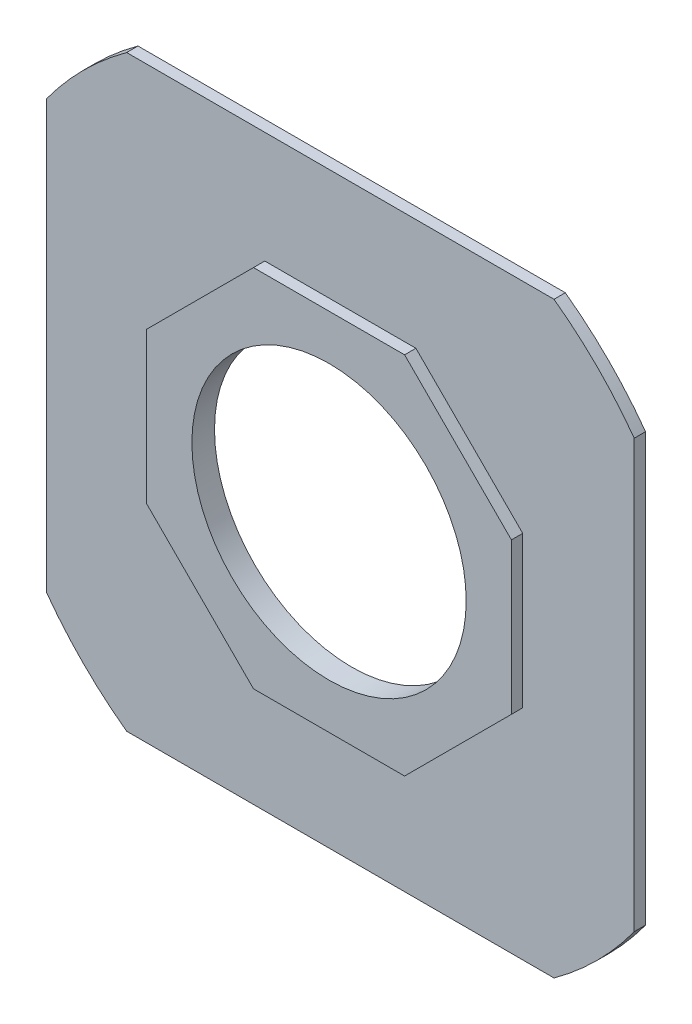
SolidWorks part; units mm, degrees
ref_plane "Front Plane" through (0, 0, 0) normal (0, 0, 1) x (1, 0, 0)
ref_plane "Top Plane" through (0, 0, 0) normal (0, 1, 0) x (1, 0, 0)
ref_plane "Right Plane" through (0, 0, 0) normal (1, 0, 0) x (0, 0, -1)
sketch "Sketch1" plane through (0, 0, 0) normal (0, 0, 1) x (1, 0, 0)
  line L1 (21.2077, 51.2) -> (-21.2077, 51.2)
  line L2 (-21.2077, 51.2) -> (-51.2, 21.2077)
  line L3 (-51.2, 21.2077) -> (-51.2, -21.2077)
  line L4 (-51.2, -21.2077) -> (-21.2077, -51.2)
  line L5 (-21.2077, -51.2) -> (21.2077, -51.2)
  line L6 (21.2077, -51.2) -> (51.2, -21.2077)
  line L7 (51.2, -21.2077) -> (51.2, 21.2077)
  line L8 (51.2, 21.2077) -> (21.2077, 51.2)
  line L9 (101.9739, -101.9739) -> (-101.9739, -101.9739)
  line L10 (101.9739, -101.9739) -> (101.9739, 101.9739)
  line L11 (101.9739, 101.9739) -> (-101.9739, 101.9739)
  line L12 (-101.9739, -101.9739) -> (-101.9739, 101.9739)
  line L13 (101.9739, -101.9739) -> (-101.9739, 101.9739) construction
  line L14 (101.9739, 101.9739) -> (-101.9739, -101.9739) construction
  circle A0 centre (0, 0) radius 38.5
  circle A1 centre (0, 0) radius 51.2 construction
  dimension "D1" = 77
  dimension "D2" = 12.7
extrude "Boss-Extrude1" add sketch "Sketch1" along normal blind 3.175 contours L7 L8 L1 L2 L3 L4 L5 L6 A0 | L12 L9 L10 L11 L8 L7 L6 L5 L4 L3 L2 L1 region at (35.1799, 35.1799, 0) region at (0, -99.0896, 0)
extrude "Boss-Extrude2" add sketch "Sketch1<3>" along normal blind 6.35 contours L7 L8 L1 L2 L3 L4 L5 L6 A0 region at (35.1799, 35.1799, 0)
sketch "Sketch1<3>" plane through (0, 0, 0) normal (0, 0, 1) x (1, 0, 0) same geometry as "Sketch1"
sketch "Sketch6" plane through (0, 0, 0) normal (0, 0, -1) x (-1, 0, 0)
  line L0 (-81, 59.4916) -> (-81, -59.4916) construction
  line L1 (-59.4916, 81) -> (59.4916, 81) construction
  line L2 (81, 59.4916) -> (81, -59.4916) construction
  line L3 (-59.4916, -81) -> (59.4916, -81) construction
  line L4 (-82.5, 59.9812) -> (-82.5, -59.9812)
  line L5 (-59.9812, -82.5) -> (59.9812, -82.5)
  line L6 (82.5, 59.9812) -> (82.5, -59.9812)
  line L7 (-59.9812, 82.5) -> (59.9812, 82.5)
  arc A1 (-59.4916, 81) -> (-81, 59.4916) centre (0, 0) ccw construction
  arc A2 (81, 59.4916) -> (59.4916, 81) centre (0, 0) ccw construction
  arc A3 (59.4916, -81) -> (81, -59.4916) centre (0, 0) ccw construction
  arc A4 (-81, -59.4916) -> (-59.4916, -81) centre (0, 0) ccw construction
  circle A5 centre (0, 0) radius 81 construction
  circle A6 centre (-63.2861, 63.2861) radius 11 construction
  arc A7 (-82.5, -59.9812) -> (-59.9812, -82.5) centre (0, 0) ccw
  arc A8 (59.9812, -82.5) -> (82.5, -59.9812) centre (0, 0) ccw
  arc A9 (82.5, 59.9812) -> (59.9812, 82.5) centre (0, 0) ccw
  arc A10 (-59.9812, 82.5) -> (-82.5, 59.9812) centre (0, 0) ccw
  line M18 (101.9739, -101.9739) -> (101.9739, 101.9739)
  line M19 (101.9739, 101.9739) -> (-101.9739, 101.9739)
  line M20 (-101.9739, 101.9739) -> (-101.9739, -101.9739)
  line M21 (-101.9739, -101.9739) -> (101.9739, -101.9739)
  dimension "D1" = 1.5
extrude "Cut-Extrude1" cut sketch "Sketch6" against normal blind 15 contours A10 L7 A9 L6 A8 L5 A7 L4 M21 M18 M19 M20 region at (0, -99.0896, 0)
